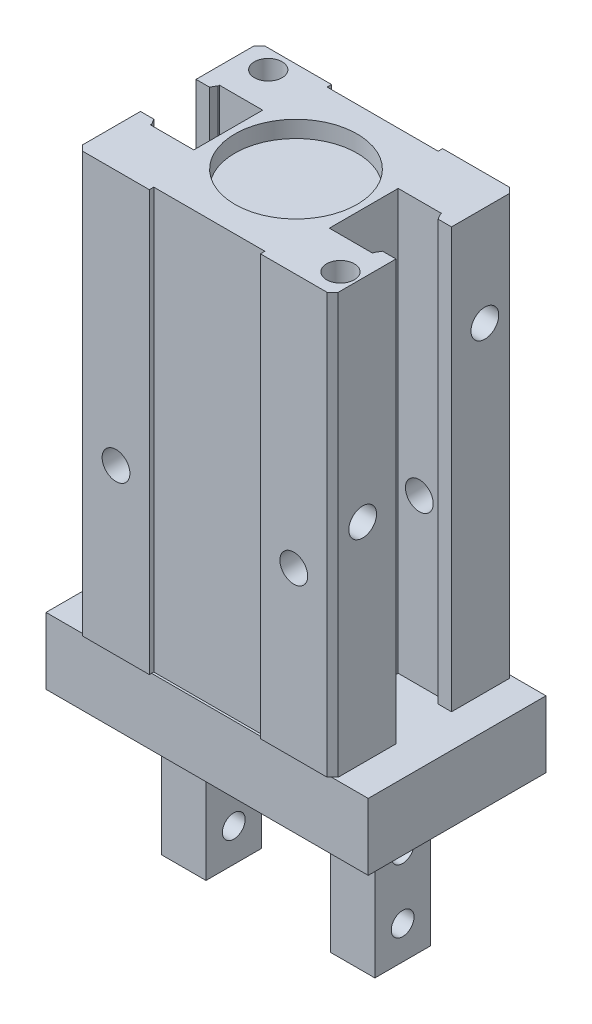
SolidWorks part; units mm, degrees
material "铝合金-阳极处理"
ref_plane "前基準面" through (0, 0, 0) normal (0, 0, 1) x (1, 0, 0)
ref_plane "上基準面" through (0, 0, 0) normal (0, 1, 0) x (1, 0, 0)
ref_plane "右基準面" through (0, 0, 0) normal (1, 0, 0) x (0, 0, -1)
sketch "草图1" plane through (0, 0, 0) normal (0, 0, 1) x (1, 0, 0)
  line L1 (0, 0) -> (23, 0)
  line L2 (0, 0) -> (0, 37.8)
  line L3 (0, 37.8) -> (23, 37.8)
  line L4 (23, 0) -> (23, 37.8)
  dimension "D1" = 23
  dimension "D2" = 37.8
extrude "拉伸1" add sketch "草图1" along normal blind 16.4
sketch "草图19" plane through (0, 0, 0) normal (0, -1, 0) x (1, 0, 0)
  line L0 (23, 8.2) -> (0, 8.2) construction
  line L1 (-3, 0.2) -> (26, 0.2)
  line L2 (-3, 0.2) -> (-3, 16.2)
  line L3 (-3, 16.2) -> (26, 16.2)
  line L4 (26, 0.2) -> (26, 16.2)
  line L5 (23, 16.4) -> (23, 0) construction
  line L6 (0, 16.4) -> (0, 0) construction
  line L7 (11.5, 8.2) -> (11.5, 1.799) construction
  dimension "D1" = 29
  dimension "D2" = 16
extrude "拉伸3" add sketch "草图19" along normal blind 6
sketch "草图5" plane through (0, -6, 0) normal (0, -1, 0) x (1, 0, 0)
  line L0 (11.5, 16.2) -> (11.5, 0.2) construction
  line L1 (1.9, 5.7) -> (5.9, 5.7)
  line L2 (1.9, 5.7) -> (1.9, 10.7)
  line L3 (1.9, 10.7) -> (5.9, 10.7)
  line L4 (5.9, 5.7) -> (5.9, 10.7)
  line L7 (11.5, 8.2) -> (0.9111, 8.2) construction
  line L8 (17.1, 5.7) -> (17.1, 10.7)
  line L9 (21.1, 10.7) -> (17.1, 10.7)
  line L10 (21.1, 5.7) -> (21.1, 10.7)
  line L11 (21.1, 5.7) -> (17.1, 5.7)
  line L12 (26, 16.2) -> (-3, 16.2) construction
  line L13 (-3, 0.2) -> (26, 0.2) construction
  dimension "D1" = 4
  dimension "D2" = 5
  dimension "D3" = 11.2
extrude "拉伸2" add sketch "草图5" along normal blind 13.2
sketch "草图20" plane through (0, 0, 10.7) normal (0, 0, 1) x (1, 0, 0)
  line L0 (1.9, -19.2) -> (1.9, -6) construction
  line L1 (1.9, -7.2) -> (-1, -7.2)
  line L2 (1.9, -7.2) -> (1.9, -6)
  line L3 (1.9, -6) -> (-1, -6)
  line L4 (-1, -7.2) -> (-1, -6)
  line L5 (26, -6) -> (-3, -6) construction
  line L6 (5.9, -19.2) -> (5.9, -6) construction
  line L7 (5.9, -7.2) -> (11, -7.2)
  line L8 (5.9, -7.2) -> (5.9, -6)
  line L9 (5.9, -6) -> (11, -6)
  line L10 (11, -7.2) -> (11, -6)
  line L11 (11.5, -6) -> (11.5, -13.2643) construction
  line L12 (12, -7.2) -> (12, -6)
  line L13 (17.1, -6) -> (12, -6)
  line L14 (17.1, -7.2) -> (17.1, -6)
  line L15 (17.1, -7.2) -> (12, -7.2)
  line L16 (24, -7.2) -> (24, -6)
  line L17 (21.1, -6) -> (24, -6)
  line L18 (21.1, -7.2) -> (21.1, -6)
  line L19 (21.1, -7.2) -> (24, -7.2)
  line L21 (5.9, -19.2) -> (1.9, -19.2) construction
  dimension "D1" = 2.9
  dimension "D2" = 12
  dimension "D3" = 12
extrude "拉伸4" add sketch "草图20" against normal up to surface (5 mm away) up to face at (19.1, -12.6, 5.7)
hole_wizard "M2.5 螺纹孔1" positions "草图7" profile "草图6" tap size "M2.5" standard "ISO" end condition through all
sketch "草图7" plane through (21.1, 0, 0) normal (1, 0, 0) x (0, 0, -1)
  line L0 (-8.2, -19.2) -> (-8.2, -3.2485) construction
  line L1 (-5.7, -19.2) -> (-10.7, -19.2) construction
  point P0 (-8.2, -16.2)
  point P8 (-8.2, -10.5)
  dimension "D1" = 3
  dimension "D2" = 5.7
sketch "草图6" plane through (21.1, -16.2, 8.2) normal (0, 1, 0) x (0, 0, -1)
  line L0 (0, 0) -> (0, 24.1)
  line L1 (0, 24.1) -> (1.025, 24.1)
  line L2 (1.025, 24.1) -> (1.025, 0)
  line L5 (1.025, 0) -> (0, 0)
  line L11 (0, -6.35) -> (0, 107.95) construction
  dimension "籵謂蹟恇謂郰芛眻噤" = 2.05
  dimension "籵謂蹟恇謂郰芛旮僅" = 24.1
cosmetic thread "孔螺蚊线19" parameters "D2"=2.5
cosmetic thread "孔螺蚊线20" parameters "D2"=2.5
hole_wizard "M3 螺纹孔6" positions "草图22" profile "草图21" tap size "M3" standard "ISO"
sketch "草图22" plane through (23, 0, 0) normal (1, 0, 0) x (0, 0, -1)
  line L0 (-8.2, 37.8) -> (-8.2, 12.3025) construction
  line L1 (-16.4, 37.8) -> (0, 37.8) construction
  point P0 (-2.7, 28.8)
  point P2 (-13.7, 18.8)
  dimension "D1" = 5.5
  dimension "D2" = 11
  dimension "D3" = 9
  dimension "D4" = 19
sketch "草图21" plane through (23, 28.8, 2.7) normal (0, 1, 0) x (0, 0, -1)
  line L0 (0, 0) -> (0, 8.2511)
  line L1 (0, 8.2511) -> (1.25, 7.5)
  line L2 (1.25, 7.5) -> (1.25, 0)
  line L5 (1.25, 0) -> (0, 0)
  line L10 (0, 8.2511) -> (-1.25, 7.5) construction
  line L11 (0, -6.35) -> (0, 107.95) construction
  dimension "蹟恇謂郰芛眻噤" = 2.5
  dimension "蹟恇謂郰芛旮僅" = 7.5
  dimension "絳芛褒僅" = 118
cosmetic thread "孔螺蚊线32" parameters "D1"=6, "D2"=3
cosmetic thread "孔螺蚊线33" parameters "D1"=6, "D2"=3
hole_wizard "M3 螺纹孔7" positions "草图24" profile "草图23" tap size "M3" standard "ISO"
sketch "草图24" plane through (0, 0, 0) normal (-1, 0, 0) x (0, 0, 1)
  line L0 (8.2, 0) -> (8.2, 20.1509) construction
  line L1 (16.2, 0) -> (0.2, 0) construction
  line L3 (16.4, 37.8) -> (0, 37.8) construction
  point P0 (2.5, 10.8)
  point P8 (13.9, 10.8)
  dimension "D1" = 11.4
  dimension "D2" = 27
sketch "草图23" plane through (0, 10.8, 2.5) normal (0, 1, 0) x (0, 0, 1)
  line L0 (0, 0) -> (0, 8.2511)
  line L1 (0, 8.2511) -> (1.25, 7.5)
  line L2 (1.25, 7.5) -> (1.25, 0)
  line L5 (1.25, 0) -> (0, 0)
  line L10 (0, 8.2511) -> (-1.25, 7.5) construction
  line L11 (0, -6.35) -> (0, 107.95) construction
  dimension "蹟恇謂郰芛眻噤" = 2.5
  dimension "蹟恇謂郰芛旮僅" = 7.5
  dimension "絳芛褒僅" = 118
cosmetic thread "孔螺蚊线34" parameters "D1"=6, "D2"=3
cosmetic thread "孔螺蚊线35" parameters "D1"=6, "D2"=3
hole_wizard "M3 螺纹孔5" positions "草图9" profile "草图8" tap size "M3" standard "ISO" end condition through all
sketch "草图9" plane through (0, 0, 16.4) normal (0, 0, 1) x (1, 0, 0)
  line L0 (11.5, 9.0566) -> (11.5, 37.8) construction
  line L3 (23, 37.8) -> (0, 37.8) construction
  line L4 (23, 37.8) -> (0, 37.8) construction
  point P0 (3.5, 14.8)
  point P8 (19.5, 14.8)
  dimension "D1" = 16
  dimension "D2" = 23
sketch "草图8" plane through (3.5, 14.8, 16.4) normal (1, 0, 0) x (0, -1, 0)
  line L0 (0, 0) -> (0, 16.4)
  line L1 (0, 16.4) -> (1.25, 16.4)
  line L2 (1.25, 16.4) -> (1.25, 0)
  line L5 (1.25, 0) -> (0, 0)
  line L11 (0, -6.35) -> (0, 107.95) construction
  dimension "籵謂蹟恇謂郰芛眻噤" = 2.5
  dimension "籵謂蹟恇謂郰芛旮僅" = 16.4
cosmetic thread "孔螺蚊线30" parameters "D2"=3
cosmetic thread "孔螺蚊线31" parameters "D2"=3
sketch "草图15" plane through (0, 37.8, 0) normal (0, 1, 0) x (1, 0, 0)
  line L0 (11.5, -16.4) -> (11.5, 0) construction
  line L1 (23, -16.4) -> (0, -16.4) construction
  line L2 (23, 0) -> (0, 0) construction
  circle A0 centre (11.5, -8.2) radius 5.5
  dimension "D1" = 11
extrude "切除-拉伸4" cut sketch "草图15" against normal blind 1.5
hole_wizard "M3 螺纹孔4" positions "草图17" profile "草图16" tap size "M3" standard "ISO"
sketch "草图17" plane through (0, 37.8, 0) normal (0, 1, 0) x (-1, 0, 0)
  line L0 (-11.5, 16.4) -> (-11.5, 0) construction
  line L1 (-23, 16.4) -> (0, 16.4) construction
  line L2 (-23, 0) -> (0, 0) construction
  line L5 (-11.5, 8.2) -> (-28, 8.2) construction
  point P0 (-2.5, 1.7)
  point P15 (-21.5, 14.2)
  dimension "D1" = 20
  dimension "D2" = 18
  dimension "D3" = 12
  dimension "D4" = 13
sketch "草图16" plane through (2.5, 37.8, 1.7) normal (1, 0, 0) x (0, 0, 1)
  line L0 (0, 0) -> (0, 8.2511)
  line L1 (0, 8.2511) -> (1.25, 7.5)
  line L2 (1.25, 7.5) -> (1.25, 0)
  line L5 (1.25, 0) -> (0, 0)
  line L10 (0, 8.2511) -> (-1.25, 7.5) construction
  line L11 (0, -6.35) -> (0, 107.95) construction
  dimension "蹟恇謂郰芛眻噤" = 2.5
  dimension "蹟恇謂郰芛旮僅" = 7.5
  dimension "絳芛褒僅" = 118
cosmetic thread "孔螺蚊线28" parameters "D1"=6, "D2"=3
cosmetic thread "孔螺蚊线29" parameters "D1"=6, "D2"=3
sketch "草图18" plane through (0, 37.8, 0) normal (0, 1, 0) x (1, 0, 0)
  line L0 (11.5, -16.4) -> (11.5, 0) construction
  line L1 (23, -16.4) -> (0, -16.4) construction
  line L2 (23, 0) -> (0, 0) construction
  line L3 (11.5, -8.2) -> (23, -8.2) construction
  line L4 (23, -16.4) -> (23, 0) construction
  line L5 (23, -10.7) -> (23, -5.7)
  line L6 (23, -5.7) -> (21.5, -5.7)
  line L7 (21.5, -5.7) -> (21.5, -5.1)
  line L8 (21.5, -5.1) -> (17.6, -5.1)
  line L9 (17.6, -5.1) -> (17.6, -11.3)
  line L10 (21.5, -11.3) -> (17.6, -11.3)
  line L11 (21.5, -10.7) -> (21.5, -11.3)
  line L12 (23, -10.7) -> (21.5, -10.7)
  line L13 (0, -10.7) -> (1.5, -10.7)
  line L14 (1.5, -10.7) -> (1.5, -11.3)
  line L15 (1.5, -11.3) -> (5.4, -11.3)
  line L16 (5.4, -5.1) -> (5.4, -11.3)
  line L17 (1.5, -5.1) -> (5.4, -5.1)
  line L18 (1.5, -5.7) -> (1.5, -5.1)
  line L19 (0, -5.7) -> (1.5, -5.7)
  line L20 (0, -10.7) -> (0, -5.7)
  point P16 (17.6, -8.2)
  point P19 (5.4, -8.2)
  dimension "D1" = 5
  dimension "D3" = 5.4
  dimension "D2" = 6.2
  dimension "D4" = 1.5
extrude "切除-拉伸5" cut sketch "草图18" against normal up to surface (37.8 mm away) up to face at (-1.5, 0, 8.2)
chamfer "倒角1" distance 0.5 angle 30 2 edges at (1.5, 18.9, 5.7) (21.5, 18.9, 10.7)
chamfer "倒角2" distance 0.5 angle 30 2 edges at (21.5, 18.9, 5.7) (1.5, 18.9, 10.7)
sketch "草图25" plane through (0, 37.8, 0) normal (0, 1, 0) x (1, 0, 0)
  line L0 (23, 0) -> (0, 0) construction
  line L1 (6.5, 0) -> (16.5, 0)
  line L2 (6.5, 0) -> (6.5, -0.4)
  line L3 (6.5, -0.4) -> (16.5, -0.4)
  line L4 (16.5, 0) -> (16.5, -0.4)
  line L5 (11.5, -16.4) -> (11.5, 0) construction
  line L6 (23, -16.4) -> (0, -16.4) construction
  line L7 (11.5, -8.2) -> (-4.949, -8.2) construction
  line L8 (16.5, -16.4) -> (16.5, -16)
  line L9 (6.5, -16) -> (16.5, -16)
  line L10 (6.5, -16.4) -> (6.5, -16)
  line L11 (6.5, -16.4) -> (16.5, -16.4)
  dimension "D1" = 10
  dimension "D2" = 15.6
extrude "切除-拉伸6" cut sketch "草图25" against normal up to surface (37.8 mm away) up to face at (0.9445, 0, 8.2)
chamfer "倒角3" distance 0.5 angle 45 4 edges at (23, 18.9, 16.4) (23, 18.9, 0) (0, 18.9, 0) (0, 18.9, 16.4)
